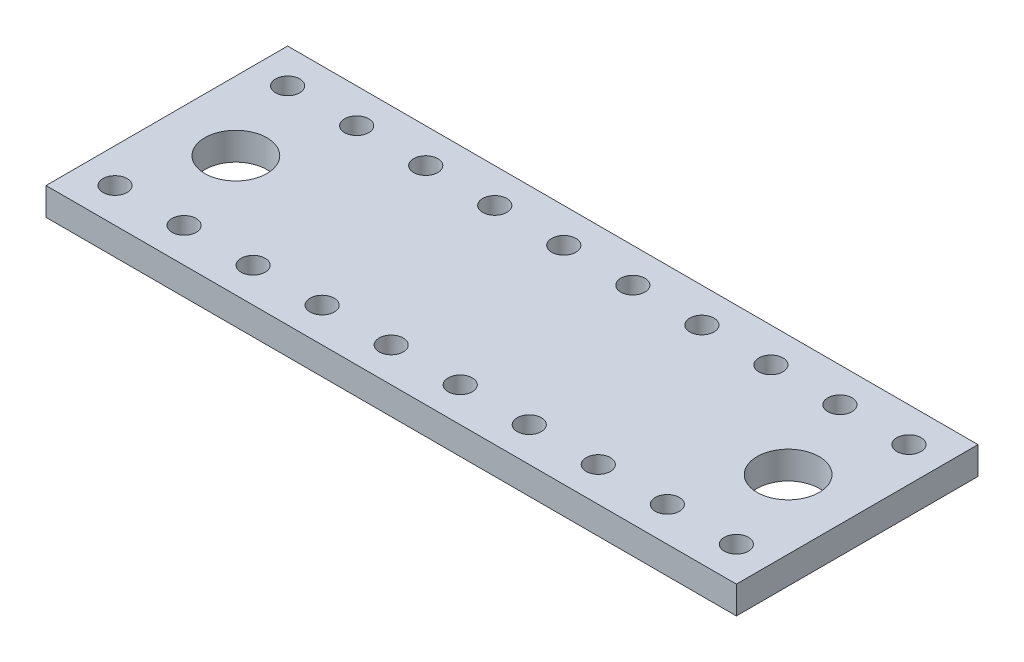
SolidWorks part; units mm, degrees
material "Plain Carbon Steel"
ref_plane "Front Plane" through (0, 0, 0) normal (0, 0, 1) x (1, 0, 0)
ref_plane "Top Plane" through (0, 0, 0) normal (0, 1, 0) x (1, 0, 0)
ref_plane "Right Plane" through (0, 0, 0) normal (1, 0, 0) x (0, 0, -1)
sketch "Sketch1" plane through (0, 0, 0) normal (0, 1, 0) x (1, 0, 0)
  line L1 (0, 0) -> (100, 0)
  line L2 (0, 0) -> (0, 35)
  line L3 (0, 35) -> (100, 35)
  line L4 (100, 0) -> (100, 35)
  dimension "D1" = 100
  dimension "D2" = 35
extrude "Boss-Extrude1" add sketch "Sketch1" along normal blind 4
ref_plane "Plane1" through (0, 0, -17.5) normal (0, 0, -1) x (-1, 0, 0)
ref_plane "Plane2" through (50, 0, 0) normal (1, 0, 0) x (0, 0, -1)
sketch "Sketch2" plane through (0, 4, 0) normal (0, 1, 0) x (1, 0, 0)
  line L0 (5, 30) -> (5, 35) construction
  line L3 (100, 35) -> (0, 35) construction
  line L4 (5, 30) -> (0, 30) construction
  line L5 (0, 35) -> (0, 0) construction
  line L6 (10, 17.5) -> (0, 17.5) construction
  line L7 (50, 35) -> (50, 0)
  line L8 (0, 0) -> (100, 0) construction
  circle A0 centre (10, 17.5) radius 4.5
  circle A1 centre (5, 30) radius 1.75
  dimension "D1" = 9
  dimension "D2" = 3.5
  dimension "D3" = 5
  dimension "D5" = 10
extrude "Cut-Extrude1" cut sketch "Sketch2" against normal through all both and the other way through all contours A1 region at (5, 4, -30)
pattern_linear "LPattern1" count 10 spacing 10 along (1, 0, 0) of "Cut-Extrude1"
mirror "Mirror1" about plane through (0, 0, -17.5) normal (0, 0, -1) of "LPattern1"
sketch "Sketch4" plane through (0, 4, 0) normal (0, 1, 0) x (1, 0, 0)
  line L0 (2.2, 17.5) -> (-2.2, 17.5) construction
  line L1 (50, 17.5) -> (50, 35) construction
  line L2 (100, 35) -> (0, 35) construction
  circle A0 centre (50, 17.5) radius 2.5
  point P4 (0, 0)
  dimension "D1" = 5
extrude "Cut-Extrude3" cut sketch "Sketch2<3>" against normal blind 4 contours A0 region at (10, 4, -17.5)
sketch "Sketch2<3>" plane through (0, 4, 0) normal (0, 1, 0) x (1, 0, 0) same geometry as "Sketch2"
mirror "Mirror2" about plane through (50, 0, 0) normal (1, 0, 0) of "Cut-Extrude3"
